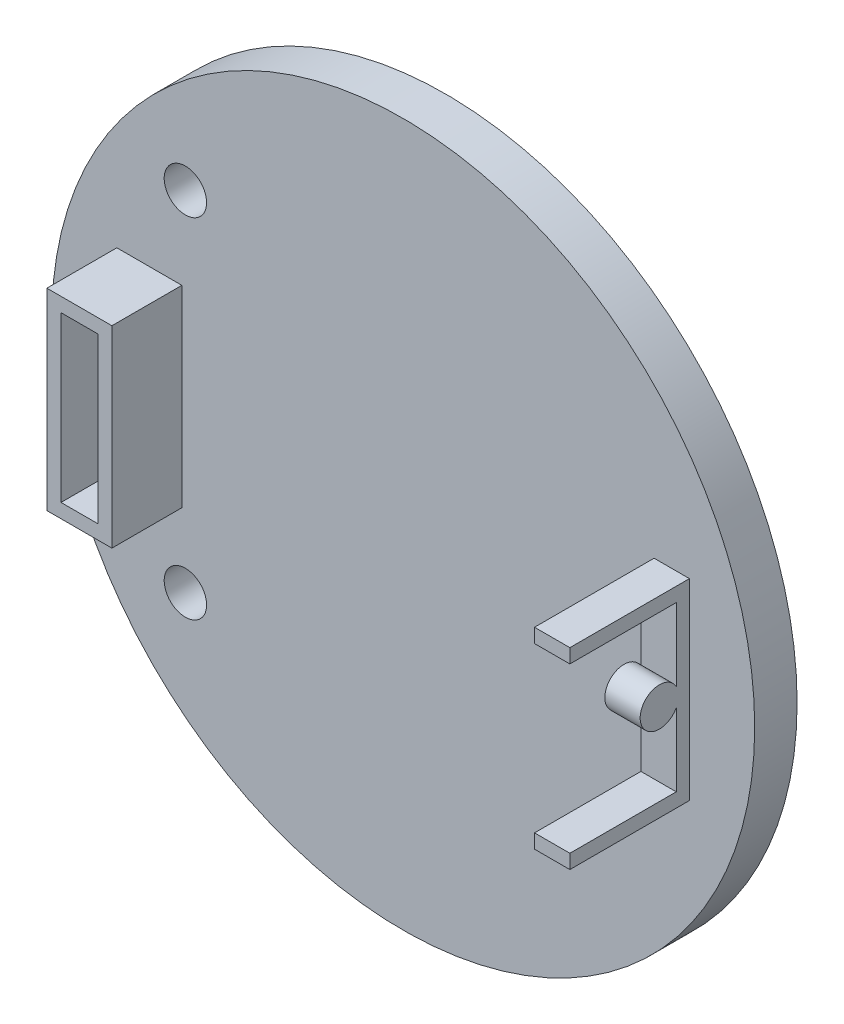
SolidWorks part; units mm, degrees
ref_plane "Front Plane" through (0, 0, 0) normal (0, 0, 1) x (1, 0, 0)
ref_plane "Top Plane" through (0, 0, 0) normal (0, 1, 0) x (1, 0, 0)
ref_plane "Right Plane" through (0, 0, 0) normal (1, 0, 0) x (0, 0, -1)
sketch "Sketch1" plane through (0, 0, 0) normal (0, 0, 1) x (1, 0, 0)
  line L0 (-1000, 0) -> (49000, 0) construction
  line L1 (17.755, 6.8) -> (20.255, 6.8)
  line L2 (17.755, 6.8) -> (17.755, -6.8)
  line L3 (17.755, -6.8) -> (20.255, -6.8)
  line L4 (20.255, 6.8) -> (20.255, -6.8)
  circle A0 centre (0, 0) radius 24.875
  point P7 (20.255, 0)
  point P10 (24.875, 0)
  dimension "D1" = 49.75
  dimension "D2" = 6.8
  dimension "D3" = 6.8
  dimension "D4" = 20.255
  dimension "D5" = 2.5
sketch "Sketch2" plane through (0, 0, 0) normal (0, 0, 1) x (1, 0, 0)
extrude "Boss-Extrude2" add sketch "Sketch1" against normal blind 3 contours A0
extrude "Boss-Extrude3" add sketch "Sketch1<4>" along normal blind 8.46 contours L2 L3 L4 L1
sketch "Sketch1<4>" plane through (0, 0, 0) normal (0, 0, 1) x (1, 0, 0) same geometry as "Sketch1"
sketch "Sketch4" plane through (20.255, 0, 0) normal (1, 0, 0) x (0, 0, -1)
  line L0 (0, 6.8) -> (0, 0.65)
  line L1 (0, 6.8) -> (0, -6.8) construction
  line L2 (0, -0.65) -> (0, -6.8)
  line L3 (0, 24.875) -> (0, -24.875) construction
  line L7 (0, 0.65) -> (-0.9313, 0.65) construction
  line L8 (-0.9313, 0.65) -> (-0.9313, -0.65) construction
  line L9 (-0.9313, -0.65) -> (0, -0.65) construction
  line L10 (-0.9313, 0.65) -> (0, 0.65)
  line L11 (-0.9313, -0.65) -> (0, -0.65)
  line L12 (0, 6.8) -> (-8.46, 6.8)
  line L13 (-8.46, 6.8) -> (-8.46, 5.8)
  line L14 (-8.46, 6.8) -> (-8.46, -6.8) construction
  line L15 (-8.46, 5.8) -> (-0.9313, 5.8)
  line L16 (-0.9313, 5.8) -> (-0.9313, 0.65)
  line L17 (-0.9313, -0.65) -> (-0.9313, -5.8)
  line L19 (-0.9313, -5.8) -> (-8.46, -5.8)
  line L20 (-8.46, -5.8) -> (-8.46, -6.8)
  line L21 (-8.46, -6.8) -> (0, -6.8)
  arc A4 (-0.9313, -0.65) -> (-0.9313, 0.65) centre (-2.1259, 0) cw
  point P15 (-0.9313, 0)
  line M8 (-8.46, 6.8) -> (-8.46, -6.8)
  dimension "D1" = 0.65
  dimension "D2" = 1.36
  dimension "D3" = 1
  dimension "D4" = 1
extrude "Cut-Extrude1" cut sketch "Sketch4" against normal up to surface (2.5 mm away) contours L17 A4 L16 L15 L19 M8 region at (20.255, 0, 4.8717) up to face at (17.755, 0, 4.23)
sketch "Sketch5" plane through (0, 0, 0) normal (0, 0, 1) x (1, 0, 0)
  line L1 (-20.26, 6.815) -> (-15.66, 6.815)
  line L2 (-20.26, 6.815) -> (-20.26, -6.815)
  line L3 (-20.26, -6.815) -> (-15.66, -6.815)
  line L4 (-15.66, 6.815) -> (-15.66, -6.815)
  point P4 (0, 0)
  dimension "D1" = 20.26
  dimension "D2" = 4.6
  dimension "D3" = 13.63
  dimension "D4" = 6.815
sketch "Sketch6" plane through (0, 0, 0) normal (0, 0, 1) x (1, 0, 0)
extrude "Boss-Extrude4" add sketch "Sketch5" along normal blind 4.95
sketch "Sketch9" plane through (0, 0, 4.95) normal (0, 0, 1) x (1, 0, 0)
  line L0 (-15.66, 6.815) -> (-20.26, 6.815) construction
  line L1 (-19.26, 5.815) -> (-16.66, 5.815)
  line L2 (-19.26, 5.815) -> (-19.26, -5.815)
  line L3 (-19.26, -5.815) -> (-16.66, -5.815)
  line L4 (-16.66, 5.815) -> (-16.66, -5.815)
  line L5 (-15.66, -6.815) -> (-15.66, 6.815) construction
  line L6 (-20.26, 6.815) -> (-20.26, -6.815) construction
  line L8 (-20.26, -6.815) -> (-15.66, -6.815) construction
  point P12 (-17.96, -6.815)
  dimension "D1" = 1
  dimension "D2" = 1
  dimension "D3" = 1
  dimension "D4" = 1
extrude "Cut-Extrude2" cut sketch "Sketch9" against normal up to surface (7.95 mm away) up to face at (24.875, 0, -3)
sketch "Sketch10" plane through (0, 0, 0) normal (0, 0, 1) x (1, 0, 0)
  circle A0 centre (-15.4092, 12.7514) radius 1.5
  circle A1 centre (-15.4092, -11.8993) radius 1.5
  dimension "D1" = 3
  dimension "D2" = 3
extrude "Cut-Extrude3" cut sketch "Sketch10" against normal blind 4.95
